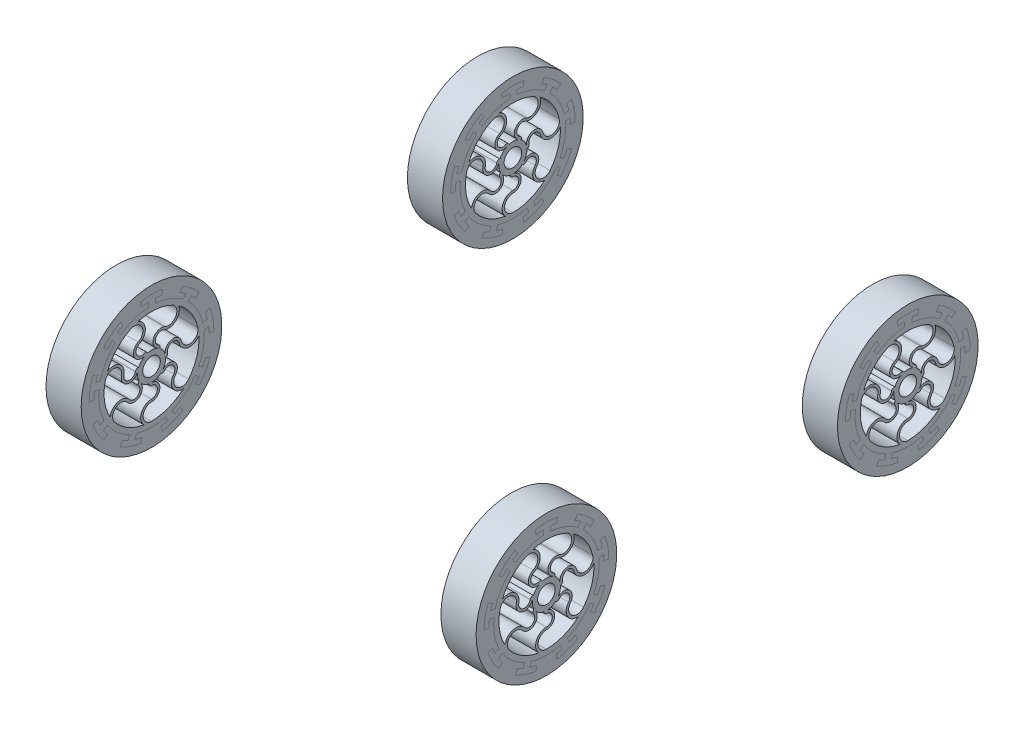
SolidWorks part; units mm, degrees
ref_plane "Front Plane" through (0, 0, 0) normal (0, 0, 1) x (1, 0, 0)
ref_plane "Top Plane" through (0, 0, 0) normal (0, 1, 0) x (1, 0, 0)
ref_plane "Right Plane" through (0, 0, 0) normal (1, 0, 0) x (0, 0, -1)
ref_plane "Plane1" through (64.95, 0, 0) normal (1, 0, 0) x (0, 0, -1)
sketch "Sketch1" plane through (64.95, 0, 0) normal (1, 0, 0) x (0, 0, -1)
  circle A0 centre (0, 0) radius 25.4 construction
  circle A1 centre (0, 0) radius 3.175
  circle A2 centre (0, 0) radius 5.08
  circle A3 centre (0, 0) radius 19.05
  circle A4 centre (0, 0) radius 17.145
  dimension "D1" = 50.8
  dimension "D2" = 38.1
  dimension "D3" = 34.29
  dimension "D4" = 6.35
  dimension "D5" = 10.16
extrude "Boss-Extrude1" add sketch "Sketch1" along normal blind 12.7 contours A3 A4 | A2 A1 region at (64.95, 0, 4.9363) region at (64.95, 0, 18.5112)
sketch "Sketch2" plane through (64.95, 0, 0) normal (1, 0, 0) x (0, 0, -1)
  circle A0 centre (0, 0) radius 5.08
  circle A1 centre (0, 0) radius 17.145
  arc A2 (0, -11.1125) -> (0, -5.08) centre (0, -8.0963) ccw
  arc A3 (0, -11.1125) -> (0, -17.145) centre (0, -14.1288) ccw
  arc A6 (0, -10.2235) -> (-2.7239, -16.9272) centre (0, -14.1288) ccw
  arc A7 (0, -10.2235) -> (0, -5.969) centre (0, -8.0963) ccw
  arc A8 (0, -5.969) -> (-0.8856, -5.0022) centre (0, -5.08) cw
  dimension "D1" = 10.16
  dimension "D2" = 34.29
  dimension "D3" = 0.889
  dimension "D4" = 0
extrude "Boss-Extrude2" add sketch "Sketch2" along normal up to surface (12.7 mm away) contours A8 A7 A6 A1 A3 A2 A0 region at (64.95, -10.6813, 0.5074) up to face at (77.65, 0, -3.175)
pattern_circular "CirPattern1" count 7 over 360 about axis through (77.65, 0, 0) along (1, 0, 0) of "Boss-Extrude2"
sketch "Sketch3" plane through (64.95, 0, 0) normal (1, 0, 0) x (0, 0, -1)
  line L2 (-3.9449, 22.1713) -> (-3.6335, 20.4208)
  line L4 (-1.1102, 20.7118) -> (-1.1102, 19.0176)
  line L6 (3.9449, 22.1713) -> (3.6335, 20.4208)
  line L7 (1.4298, 20.6921) -> (1.4298, 18.9963)
  circle A0 centre (0, 0) radius 19.05 construction
  circle A1 centre (0, 0) radius 19.05
  arc A2 (-3.9449, 22.1713) -> (3.9449, 22.1713) centre (0, 0) cw
  arc A3 (-3.6335, 20.4208) -> (-1.1102, 20.7118) centre (0, 0) cw
  arc A4 (1.4298, 20.6921) -> (3.6335, 20.4208) centre (0, 0) cw
  dimension "D5" = 2.5401
  dimension "D1" = 2.54
  dimension "D2" = 1.778
  dimension "D3" = 2.54
  dimension "D4" = 3.175
extrude "Boss-Extrude3" add sketch "Sketch3" along a picked direction on the side of the normal blind 12.7 contours A1 L7 L6 A2 L2 A3 L4 region at (64.95, 21.1336, -0.0386)
pattern_circular "CirPattern2" count 9 over 360 about axis through (77.65, 0, 0) along (1, 0, 0) of "Boss-Extrude3"
sketch "Sketch5" plane through (64.95, 0, 0) normal (1, 0, 0) x (0, 0, -1)
  line L36 (-1.1102, 20.7118) -> (-1.1102, 19.0176)
  line L37 (-3.9449, 22.1713) -> (-3.6335, 20.4208)
  line L38 (3.6335, 20.4208) -> (3.9449, 22.1713)
  line L39 (1.4298, 18.9963) -> (1.4298, 20.6921)
  line L40 (12.4628, 16.5797) -> (11.3738, 15.282)
  line L41 (11.2294, 19.5199) -> (10.3428, 17.9787)
  line L42 (15.9096, 13.3077) -> (17.2734, 14.4484)
  line L43 (13.3059, 13.6329) -> (14.396, 14.932)
  line L44 (20.2043, 4.6899) -> (18.5359, 4.3957)
  line L45 (21.1494, 7.735) -> (19.4796, 7.1243)
  line L46 (20.7415, -0.0322) -> (22.5195, -0.035)
  line L47 (18.956, 1.8906) -> (20.6261, 2.1851)
  line L48 (18.492, -9.3944) -> (17.0248, -8.5474)
  line L49 (21.1733, -7.6692) -> (19.5016, -7.0637)
  line L50 (15.8682, -13.357) -> (17.2284, -14.502)
  line L51 (15.7363, -10.7364) -> (17.205, -11.5843)
  line L52 (8.1271, -19.083) -> (7.5476, -17.491)
  line L53 (11.29, -19.4849) -> (10.3986, -17.9465)
  line L54 (3.57, -20.432) -> (3.876, -22.1834)
  line L55 (5.1535, -18.3397) -> (5.7335, -19.9333)
  line L56 (-6.0406, -19.8424) -> (-5.4612, -18.2504)
  line L57 (-3.876, -22.1834) -> (-3.57, -20.432)
  line L58 (-10.3986, -17.9465) -> (-11.29, -19.4849)
  line L59 (-7.8407, -17.3616) -> (-8.4207, -18.9552)
  line L60 (-17.3818, -11.3173) -> (-15.9147, -10.4703)
  line L61 (-17.2284, -14.502) -> (-15.8682, -13.357)
  line L62 (-19.5016, -7.0637) -> (-21.1733, -7.6692)
  line L63 (-17.1662, -8.2599) -> (-18.6348, -9.1078)
  line L64 (-20.5899, 2.5032) -> (-18.9215, 2.2091)
  line L65 (-22.5195, -0.035) -> (-20.7415, -0.0322)
  line L66 (-19.4796, 7.1243) -> (-21.1494, 7.735)
  line L67 (-18.4594, 4.7068) -> (-20.1295, 5.0013)
  line L68 (-14.1637, 15.1525) -> (-13.0747, 13.8547)
  line L69 (-17.2734, 14.4484) -> (-15.9096, 13.3077)
  line L70 (-10.3428, 17.9787) -> (-11.2294, 19.5199)
  line L71 (-11.1153, 15.4711) -> (-12.2054, 16.7702)
  line L72 (-1.1102, 20.7118) -> (-1.1102, 19.0176)
  line L73 (-3.9449, 22.1713) -> (-3.6335, 20.4208)
  line L74 (3.6335, 20.4208) -> (3.9449, 22.1713)
  line L75 (1.4298, 18.9963) -> (1.4298, 20.6921)
  line L76 (12.4628, 16.5797) -> (11.3738, 15.282)
  line L77 (11.2294, 19.5199) -> (10.3428, 17.9787)
  line L78 (15.9096, 13.3077) -> (17.2734, 14.4484)
  line L79 (13.3059, 13.6329) -> (14.396, 14.932)
  line L80 (20.2043, 4.6899) -> (18.5359, 4.3957)
  line L81 (21.1494, 7.735) -> (19.4796, 7.1243)
  line L82 (20.7415, -0.0322) -> (22.5195, -0.035)
  line L83 (18.956, 1.8906) -> (20.6261, 2.1851)
  line L84 (18.492, -9.3944) -> (17.0248, -8.5474)
  line L85 (21.1733, -7.6692) -> (19.5016, -7.0637)
  line L86 (15.8682, -13.357) -> (17.2284, -14.502)
  line L87 (15.7363, -10.7364) -> (17.205, -11.5843)
  line L88 (8.1271, -19.083) -> (7.5476, -17.491)
  line L89 (11.29, -19.4849) -> (10.3986, -17.9465)
  line L90 (3.57, -20.432) -> (3.876, -22.1834)
  line L91 (5.1535, -18.3397) -> (5.7335, -19.9333)
  line L92 (-6.0406, -19.8424) -> (-5.4612, -18.2504)
  line L93 (-3.876, -22.1834) -> (-3.57, -20.432)
  line L94 (-10.3986, -17.9465) -> (-11.29, -19.4849)
  line L95 (-7.8407, -17.3616) -> (-8.4207, -18.9552)
  line L96 (-17.3818, -11.3173) -> (-15.9147, -10.4703)
  line L97 (-17.2284, -14.502) -> (-15.8682, -13.357)
  line L98 (-19.5016, -7.0637) -> (-21.1733, -7.6692)
  line L99 (-17.1662, -8.2599) -> (-18.6348, -9.1078)
  line L100 (-20.5899, 2.5032) -> (-18.9215, 2.2091)
  line L101 (-22.5195, -0.035) -> (-20.7415, -0.0322)
  line L102 (-19.4796, 7.1243) -> (-21.1494, 7.735)
  line L103 (-18.4594, 4.7068) -> (-20.1295, 5.0013)
  line L104 (-14.1637, 15.1525) -> (-13.0747, 13.8547)
  line L105 (-17.2734, 14.4484) -> (-15.9096, 13.3077)
  line L106 (-10.3428, 17.9787) -> (-11.2294, 19.5199)
  line L107 (-11.1153, 15.4711) -> (-12.2054, 16.7702)
  circle A0 centre (0, 0) radius 25.4
  arc A37 (-1.1102, 19.0176) -> (-11.1153, 15.4711) centre (0, 0) ccw
  arc A38 (-1.1102, 20.7118) -> (-3.6335, 20.4208) centre (0, 0) ccw
  arc A39 (3.9449, 22.1713) -> (-3.9449, 22.1713) centre (0, 0) ccw
  arc A40 (3.6335, 20.4208) -> (1.4298, 20.6921) centre (0, 0) ccw
  arc A41 (11.3738, 15.282) -> (1.4298, 18.9963) centre (0, 0) ccw
  arc A42 (12.4628, 16.5797) -> (10.3428, 17.9787) centre (0, 0) ccw
  arc A43 (17.2734, 14.4484) -> (11.2294, 19.5199) centre (0, 0) ccw
  arc A44 (15.9096, 13.3077) -> (14.396, 14.932) centre (0, 0) ccw
  arc A45 (18.5359, 4.3957) -> (13.3059, 13.6329) centre (0, 0) ccw
  arc A46 (20.2043, 4.6899) -> (19.4796, 7.1243) centre (0, 0) ccw
  arc A47 (22.5195, -0.035) -> (21.1494, 7.735) centre (0, 0) ccw
  arc A48 (20.7415, -0.0322) -> (20.6261, 2.1851) centre (0, 0) ccw
  arc A49 (17.0248, -8.5474) -> (18.956, 1.8906) centre (0, 0) ccw
  arc A50 (18.492, -9.3944) -> (19.5016, -7.0637) centre (0, 0) ccw
  arc A51 (17.2284, -14.502) -> (21.1733, -7.6692) centre (0, 0) ccw
  arc A52 (15.8682, -13.357) -> (17.205, -11.5843) centre (0, 0) ccw
  arc A53 (7.5476, -17.491) -> (15.7363, -10.7364) centre (0, 0) ccw
  arc A54 (8.1271, -19.083) -> (10.3986, -17.9465) centre (0, 0) ccw
  arc A55 (3.876, -22.1834) -> (11.29, -19.4849) centre (0, 0) ccw
  arc A56 (3.57, -20.432) -> (5.7335, -19.9333) centre (0, 0) ccw
  arc A57 (-5.4612, -18.2504) -> (5.1535, -18.3397) centre (0, 0) ccw
  arc A58 (-6.0406, -19.8424) -> (-3.57, -20.432) centre (0, 0) ccw
  arc A59 (-11.29, -19.4849) -> (-3.876, -22.1834) centre (0, 0) ccw
  arc A60 (-10.3986, -17.9465) -> (-8.4207, -18.9552) centre (0, 0) ccw
  arc A61 (-15.9147, -10.4703) -> (-7.8407, -17.3616) centre (0, 0) ccw
  arc A62 (-17.3818, -11.3173) -> (-15.8682, -13.357) centre (0, 0) ccw
  arc A63 (-21.1733, -7.6692) -> (-17.2284, -14.502) centre (0, 0) ccw
  arc A64 (-19.5016, -7.0637) -> (-18.6348, -9.1078) centre (0, 0) ccw
  arc A65 (-18.9215, 2.2091) -> (-17.1662, -8.2599) centre (0, 0) ccw
  arc A66 (-20.5899, 2.5032) -> (-20.7415, -0.0322) centre (0, 0) ccw
  arc A67 (-21.1494, 7.735) -> (-22.5195, -0.035) centre (0, 0) ccw
  arc A68 (-19.4796, 7.1243) -> (-20.1295, 5.0013) centre (0, 0) ccw
  arc A69 (-13.0747, 13.8547) -> (-18.4594, 4.7068) centre (0, 0) ccw
  arc A70 (-14.1637, 15.1525) -> (-15.9096, 13.3077) centre (0, 0) ccw
  arc A71 (-11.2294, 19.5199) -> (-17.2734, 14.4484) centre (0, 0) ccw
  arc A72 (-10.3428, 17.9787) -> (-12.2054, 16.7702) centre (0, 0) ccw
  arc A73 (-1.1102, 19.0176) -> (-11.1153, 15.4711) centre (0, 0) ccw
  arc A74 (-1.1102, 20.7118) -> (-3.6335, 20.4208) centre (0, 0) ccw
  arc A75 (3.9449, 22.1713) -> (-3.9449, 22.1713) centre (0, 0) ccw
  arc A76 (3.6335, 20.4208) -> (1.4298, 20.6921) centre (0, 0) ccw
  arc A77 (11.3738, 15.282) -> (1.4298, 18.9963) centre (0, 0) ccw
  arc A78 (12.4628, 16.5797) -> (10.3428, 17.9787) centre (0, 0) ccw
  arc A79 (17.2734, 14.4484) -> (11.2294, 19.5199) centre (0, 0) ccw
  arc A80 (15.9096, 13.3077) -> (14.396, 14.932) centre (0, 0) ccw
  arc A81 (18.5359, 4.3957) -> (13.3059, 13.6329) centre (0, 0) ccw
  arc A82 (20.2043, 4.6899) -> (19.4796, 7.1243) centre (0, 0) ccw
  arc A83 (22.5195, -0.035) -> (21.1494, 7.735) centre (0, 0) ccw
  arc A84 (20.7415, -0.0322) -> (20.6261, 2.1851) centre (0, 0) ccw
  arc A85 (17.0248, -8.5474) -> (18.956, 1.8906) centre (0, 0) ccw
  arc A86 (18.492, -9.3944) -> (19.5016, -7.0637) centre (0, 0) ccw
  arc A87 (17.2284, -14.502) -> (21.1733, -7.6692) centre (0, 0) ccw
  arc A88 (15.8682, -13.357) -> (17.205, -11.5843) centre (0, 0) ccw
  arc A89 (7.5476, -17.491) -> (15.7363, -10.7364) centre (0, 0) ccw
  arc A90 (8.1271, -19.083) -> (10.3986, -17.9465) centre (0, 0) ccw
  arc A91 (3.876, -22.1834) -> (11.29, -19.4849) centre (0, 0) ccw
  arc A92 (3.57, -20.432) -> (5.7335, -19.9333) centre (0, 0) ccw
  arc A93 (-5.4612, -18.2504) -> (5.1535, -18.3397) centre (0, 0) ccw
  arc A94 (-6.0406, -19.8424) -> (-3.57, -20.432) centre (0, 0) ccw
  arc A95 (-11.29, -19.4849) -> (-3.876, -22.1834) centre (0, 0) ccw
  arc A96 (-10.3986, -17.9465) -> (-8.4207, -18.9552) centre (0, 0) ccw
  arc A97 (-15.9147, -10.4703) -> (-7.8407, -17.3616) centre (0, 0) ccw
  arc A98 (-17.3818, -11.3173) -> (-15.8682, -13.357) centre (0, 0) ccw
  arc A99 (-21.1733, -7.6692) -> (-17.2284, -14.502) centre (0, 0) ccw
  arc A100 (-19.5016, -7.0637) -> (-18.6348, -9.1078) centre (0, 0) ccw
  arc A101 (-18.9215, 2.2091) -> (-17.1662, -8.2599) centre (0, 0) ccw
  arc A102 (-20.5899, 2.5032) -> (-20.7415, -0.0322) centre (0, 0) ccw
  arc A103 (-21.1494, 7.735) -> (-22.5195, -0.035) centre (0, 0) ccw
  arc A104 (-19.4796, 7.1243) -> (-20.1295, 5.0013) centre (0, 0) ccw
  arc A105 (-13.0747, 13.8547) -> (-18.4594, 4.7068) centre (0, 0) ccw
  arc A106 (-14.1637, 15.1525) -> (-15.9096, 13.3077) centre (0, 0) ccw
  arc A107 (-11.2294, 19.5199) -> (-17.2734, 14.4484) centre (0, 0) ccw
  arc A108 (-10.3428, 17.9787) -> (-12.2054, 16.7702) centre (0, 0) ccw
  dimension "D1" = 50.8
  dimension "D2" = 0
extrude "Boss-Extrude4" add sketch "Sketch5" along normal up to surface (12.7 mm away) separate body up to face at (77.65, -8.4949, 4.395)
sketch "Sketch4" plane through (0, 0, 0) normal (1, 0, 0) x (0, 0, -1)
  line L0 (0, 0) -> (-130.5, 0) construction
pattern_linear "LPattern1" count 2 spacing 130.5 along (0, 0, 1) of bodies 111 107
mirror "Mirror1" about plane through (0, 0, 0) normal (1, 0, 0) of bodies 107 108 112 111
